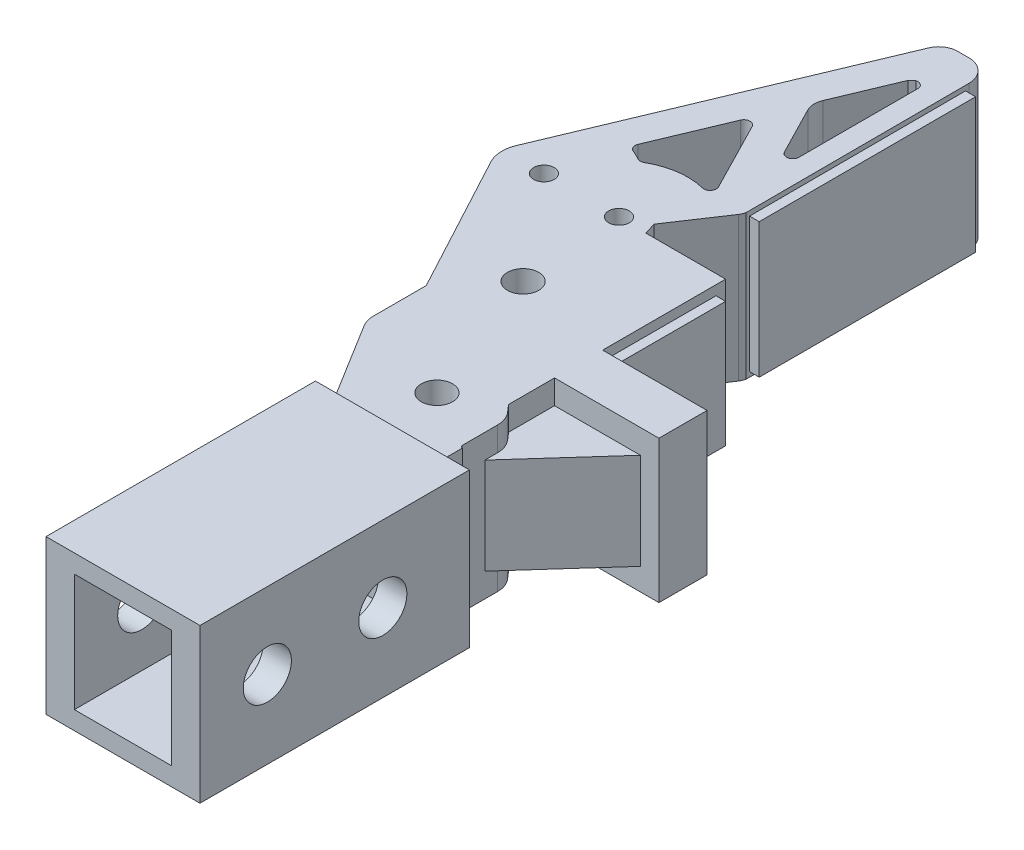
SolidWorks part; units mm, degrees
ref_plane "Alzado" through (0, 0, 0) normal (0, 0, 1) x (1, 0, 0)
ref_plane "Planta" through (0, 0, 0) normal (0, 1, 0) x (1, 0, 0)
ref_plane "Vista lateral" through (0, 0, 0) normal (1, 0, 0) x (0, 0, -1)
sketch "Croquis1" plane through (0, 0, 0) normal (0, 1, 0) x (1, 0, 0)
  line L0 (18.6195, -63.7365) -> (15.4788, -71.2468)
  line L1 (23.4981, -70.8922) -> (19.7973, -63.6902)
  line L2 (21.2126, -59.3337) -> (23.7797, -64.3294)
  line L3 (23.7582, -51.4483) -> (21.148, -57.6901)
  line L4 (25.0079, -64.0323) -> (25.0079, -51.699)
  line L9 (9.2725, -77.6641) -> (10.2186, -75.4015)
  line L10 (10.6346, -74.4068) -> (10.2186, -75.4015)
  line L11 (10.6346, -74.4068) -> (21.907, -47.451)
  line L13 (23.7058, -46.262) -> (24.8929, -46.2648)
  line L14 (27.544, -96.0434) -> (32.8286, -102.1422)
  line L15 (33.4392, -103.7794) -> (33.4392, -107.4469)
  line L16 (22.5204, -109.7992) -> (17.5627, -101.778)
  line L17 (17.1892, -89.4522) -> (17.1892, -100.4636)
  line L18 (23.7582, -51.4483) -> (24.195, -51.0698)
  line L19 (26.9334, -90.9455) -> (26.9334, -94.4063)
  line L20 (17.1892, -94.9579) -> (9.4071, -80.4546)
  line L21 (26.9334, -90.9455) -> (23.879, -78.8216)
  line L24 (22.5204, -109.7992) -> (33.6892, -109.7992)
  line L25 (33.6892, -107.6969) -> (33.6892, -109.7992)
  line L30 (23.879, -78.8216) -> (23.4981, -77.5902)
  line L31 (25.0353, -77.0872) -> (22.7227, -80.5561) construction
  line L32 (24.2033, -76.5325) -> (21.8906, -80.0014) construction
  line L35 (27.1871, -48.5593) -> (27.2389, -71.7765)
  line L36 (26.9975, -72.3412) -> (25.0143, -75.316)
  line L37 (24.2033, -76.5325) -> (25.0143, -75.316)
  line L38 (24.2033, -76.5325) -> (23.4981, -77.5902)
  line L39 (18.0704, -94.4851) -> (10.2882, -79.9818) construction
  line L40 (10.1951, -78.0499) -> (11.1412, -75.7873) construction
  line L41 (11.5572, -74.7926) -> (11.1412, -75.7873) construction
  line L42 (11.5572, -74.7926) -> (22.8287, -47.8391) construction
  line L43 (23.7035, -47.262) -> (25.2842, -47.2658) construction
  line L44 (25.0353, -77.0872) -> (25.8463, -75.8707) construction
  line L45 (27.8414, -72.8781) -> (25.8463, -75.8707) construction
  line L46 (28.1876, -48.7788) -> (28.2392, -71.8971) construction
  arc A0 (23.2652, -71.7401) -> (23.4981, -70.8922) centre (22.92, -71.1893) ccw
  arc A1 (22.7613, -71.8197) -> (22.8172, -71.8312) centre (22.92, -71.1893) ccw
  arc A2 (22.8172, -71.8312) -> (23.2652, -71.7401) centre (22.92, -71.1893) ccw
  arc A3 (22.7613, -71.8197) -> (17.441, -72.5613) centre (21.016, -78.7534) ccw
  arc A4 (17.116, -72.6484) -> (17.441, -72.5613) centre (17.116, -71.9984) ccw
  arc A5 (16.791, -72.5613) -> (17.116, -72.6484) centre (17.116, -71.9984) ccw
  arc A6 (16.791, -72.5613) -> (15.8399, -72.1022) centre (13.216, -78.7534) ccw
  arc A7 (15.4943, -71.7826) -> (15.8399, -72.1022) centre (16.0785, -71.4976) ccw
  arc A8 (15.4788, -71.2468) -> (15.4943, -71.7826) centre (16.0785, -71.4976) ccw
  arc A9 (19.7973, -63.6902) -> (19.0563, -63.358) centre (19.2191, -63.9873) ccw
  arc A10 (19.0563, -63.358) -> (18.6195, -63.7365) centre (19.2191, -63.9873) ccw
  arc A11 (24.7509, -64.5501) -> (25.0079, -64.0323) centre (24.3579, -64.0323) ccw
  arc A12 (23.7797, -64.3294) -> (24.7509, -64.5501) centre (24.3579, -64.0323) ccw
  arc A13 (21.0967, -59.058) -> (21.2126, -59.3337) centre (22.947, -58.4424) ccw
  arc A14 (21.148, -57.6901) -> (21.0967, -59.058) centre (22.947, -58.4424) ccw
  arc A15 (25.0079, -51.699) -> (24.7509, -51.1813) centre (24.3579, -51.699) ccw
  arc A16 (24.7509, -51.1813) -> (24.195, -51.0698) centre (24.3579, -51.699) ccw
  arc A20 (9.2725, -77.6641) -> (9.4071, -80.4546) centre (12.2709, -78.918) ccw
  arc A21 (23.7058, -46.262) -> (21.907, -47.451) centre (23.7012, -48.2102) ccw
  circle A23 centre (21.016, -78.7534) radius 1.0725
  circle A24 centre (13.216, -78.7534) radius 1.0725
  arc A25 (26.9334, -94.4063) -> (27.544, -96.0434) centre (29.4334, -94.4063) ccw
  arc A26 (33.4392, -103.7794) -> (32.8286, -102.1422) centre (30.9392, -103.7794) ccw
  arc A27 (33.4392, -107.4469) -> (33.6892, -107.6969) centre (33.6892, -107.4469) ccw
  arc A28 (17.1892, -100.4636) -> (17.5627, -101.778) centre (19.6892, -100.4636) ccw
  circle A33 centre (27.3927, -104.0488) radius 1.625
  circle A34 centre (21.8402, -89.5423) radius 1.625
  arc A48 (24.8929, -46.2648) -> (27.1871, -48.5593) centre (24.8875, -48.5644) cw
  arc A51 (26.9975, -72.3412) -> (27.2389, -71.7765) centre (25.0687, -71.1826) ccw
  arc A54 (10.1951, -78.0499) -> (10.2882, -79.9818) centre (12.2709, -78.918) ccw construction
  arc A55 (23.7035, -47.262) -> (22.8287, -47.8391) centre (23.7012, -48.2102) ccw construction
  arc A56 (27.1871, -48.5593) -> (25.2842, -47.2658) centre (26.1828, -47.9903) ccw construction
  arc A58 (27.8414, -72.8781) -> (28.2392, -71.8971) centre (25.0687, -71.1826) ccw construction
  arc A76 (28.1876, -48.7788) -> (24.8929, -46.2648) centre (26.1828, -47.9903) ccw construction
  dimension "D2" = 0.25
  dimension "D1" = 1
extrude "Saliente-Extruir1" add sketch "Croquis1" along normal mid plane 15
sketch "Sketch2" plane through (0, 7.5, 0) normal (0, 1, 0) x (1, 0, 0)
sketch "Sketch4" plane through (0, 7.5, 0) normal (0, 1, 0) x (1, 0, 0)
  line L0 (23.879, -78.8216) -> (32.1644, -78.8216)
  line L1 (32.1644, -78.8216) -> (32.1644, -101.3757)
  line L2 (27.544, -96.0434) -> (32.8286, -102.1422) construction
  line L3 (17.7401, -35.423) -> (25.2834, -40.7304)
  line L4 (25.2834, -40.7304) -> (17.7401, -59.6041)
  line L5 (17.7401, -59.6041) -> (17.7401, -35.423)
  line L7 (26.9334, -90.9455) -> (26.9334, -94.4063) construction
  line L9 (27.544, -96.0434) -> (32.1644, -101.3757)
  line L10 (26.9334, -90.9455) -> (26.9334, -94.4063)
  line L15 (26.9334, -90.9455) -> (23.879, -78.8216) construction
  line L16 (26.9334, -90.9455) -> (23.879, -78.8216)
  line L17 (32.9334, -90.2014) -> (29.6972, -77.3559) construction
  line L19 (32.9334, -93.1008) -> (36.699, -97.4466) construction
  line L20 (32.9334, -90.2014) -> (32.9334, -93.1008) construction
  arc A1 (26.9334, -94.4063) -> (27.544, -96.0434) centre (29.4334, -94.4063) ccw construction
  arc A3 (26.9334, -94.4063) -> (27.544, -96.0434) centre (29.4334, -94.4063) ccw
  arc A5 (26.3567, -56.7968) -> (26.4685, -56.8198) centre (26.6741, -55.5361) ccw
  arc A6 (32.9334, -93.1008) -> (32.9334, -93.1008) centre (32.9334, -93.1008) ccw
  dimension "D1" = 6
extrude "Boss-Extrude1" add sketch "Sketch4" against normal through all
sketch "Sketch7" plane through (0, 0, 109.7992) normal (0, 0, 1) x (1, 0, 0)
  line L0 (22.5204, 7.5) -> (22.5204, -7.5) construction
  line L1 (20.5204, 8) -> (20.5204, -8)
  line L2 (20.5204, -8) -> (36.5204, -8)
  line L4 (36.5204, 8) -> (36.5204, -8)
  line L5 (28.1048, 7.5) -> (28.1048, -26.4269) construction
  line L6 (22.5204, 7.5) -> (33.6892, 7.5) construction
  line L12 (20.5204, 8) -> (36.5204, 8)
  point P6 (28.1048, 0)
  dimension "D2" = 8
  dimension "D3" = 16
  dimension "D1" = 16
  dimension "D4" = 2
extrude "Boss-Extrude2" add sketch "Sketch7" along normal blind 28 contours L4 L2 L1 L12
sketch "Sketch8" plane through (20.5204, 0, 0) normal (-1, 0, 0) x (0, 0, 1)
  circle A2 centre (130.7992, 0.1) radius 2.5 construction
  circle A3 centre (118.7992, 0.1) radius 2.5 construction
  circle A4 centre (130.7992, 0.1) radius 2.5
  circle A5 centre (118.7992, 0.1) radius 2.5
sketch "Sketch9" plane through (0, 0, 137.7992) normal (0, 0, 1) x (1, 0, 0)
  line L0 (33.5704, 0) -> (30.5993, 0) construction
  line L2 (23.4704, -6.1) -> (33.5704, -6.1)
  line L9 (23.4704, -6.1) -> (23.4704, 6.1)
  line L10 (23.4704, 6.1) -> (33.5704, 6.1)
  line L14 (33.5704, -6.1) -> (33.5704, 6.1)
  line L15 (23.4704, -6.1) -> (33.5704, 6.1) construction
  line L16 (23.4704, 6.1) -> (33.5704, -6.1) construction
  line L17 (36.5204, 0) -> (35.0984, 0) construction
  line L18 (36.5204, 8) -> (36.5204, -8) construction
  line L19 (28.5204, -8) -> (28.5204, -6.7157) construction
  line L20 (20.5204, -8) -> (36.5204, -8) construction
  line L21 (28.5204, -6.1) -> (28.5204, -2.9602) construction
  point P0 (28.5204, 0)
  dimension "D1" = 10.1
  dimension "D2" = 12.2
ref_plane "Plane1" through (26.5204, 0, 0) normal (-1, 0, 0) x (0, 0, 1)
sketch "Sketch10" plane through (26.5204, 0, 0) normal (-1, 0, 0) x (0, 0, 1)
  line L0 (113.9471, 8) -> (109.7992, 7.5)
  line L1 (137.7992, 8) -> (109.7992, 8) construction
  line L2 (109.7992, 7.5) -> (109.7992, 8)
  line L3 (109.7992, 8) -> (113.9471, 8)
  line L4 (137.7992, 0) -> (128.384, 0) construction
  line L5 (137.7992, 8) -> (137.7992, -8) construction
  line L6 (113.9471, -8) -> (109.7992, -7.5)
  line L7 (109.7992, -8) -> (113.9471, -8)
  line L8 (109.7992, -7.5) -> (109.7992, -8)
extrude "Boss-Extrude3" add sketch "Sketch10" along normal mid plane 8 contours L3 L0 L2 | L6 L8 L7
extrude "Cut-Extrude6" cut sketch "Sketch8" against normal blind 30
ref_plane "Plane2" through (0, -7, 0) normal (0, -1, 0) x (-1, 0, 0)
sketch "Sketch11" plane through (0, -7, 0) normal (0, -1, 0) x (-1, 0, 0)
  line L0 (-27.1871, -48.5593) -> (-27.2389, -71.7765) construction
  line L1 (-27.1879, -48.9189) -> (-27.2381, -71.4007)
  line L3 (-27.1879, -48.9189) -> (-28.2381, -48.9189)
  line L5 (-27.2381, -71.4007) -> (-28.2381, -71.4007)
  line L6 (-28.2381, -48.9189) -> (-28.2381, -71.4007)
  dimension "D1" = 1
extrude "Boss-Extrude4" add sketch "Sketch11" against normal blind 14
sketch "Sketch12" plane through (32.1644, 0, 0) normal (1, 0, 0) x (0, 0, -1)
  line L0 (-94.9579, -7.3) -> (-100.4636, -7.3) construction
  line L5 (-78.8216, 7.5) -> (-101.3757, 7.5) construction
  line L6 (-101.6002, -7.5) -> (-101.6002, 7.5) construction
  line L17 (-96.6002, -7.3) -> (-91.6002, -7.3)
  line L18 (-91.6002, -7.3) -> (-91.6002, 7.5)
  line L19 (-91.6002, 7.5) -> (-96.6002, 7.5)
  line L20 (-96.6002, 7.5) -> (-96.6002, -7.3)
  dimension "D1" = 5
  dimension "D2" = 5
extrude "Boss-Extrude5" add sketch "Sketch12" along normal blind 10.85
sketch "Sketch13" plane through (32.1644, 0, 0) normal (1, 0, 0) x (0, 0, -1)
  line L1 (-90.6002, 6.5) -> (-79.8216, 6.5)
  line L2 (-90.6002, 6.5) -> (-90.6002, -6.5)
  line L3 (-90.6002, -6.5) -> (-79.8216, -6.5)
  line L4 (-79.8216, 6.5) -> (-79.8216, -6.5)
  line L7 (-91.6002, -7.3) -> (-91.6002, 7.5) construction
  line L8 (-78.8216, -7.5) -> (-78.8216, 7.5) construction
  line L9 (-78.8216, -7.5) -> (-101.3757, -7.5) construction
  line L10 (-78.8216, 7.5) -> (-91.6002, 7.5) construction
  dimension "D1" = 1
  dimension "D2" = 1
  dimension "D3" = 1
  dimension "D4" = 1
extrude "Boss-Extrude6" add sketch "Sketch13" along normal blind 1
sketch "Sketch14" plane through (0, 0, 0) normal (0, 1, 0) x (1, 0, 0)
  line L0 (20.5204, -109.7992) -> (20.2925, -106.1946)
  line L1 (22.5204, -109.7992) -> (17.5627, -101.778) construction
  line L2 (20.2925, -106.1946) -> (22.5204, -109.7992)
  line L3 (22.5204, -109.7992) -> (20.5204, -109.7992)
extrude "Boss-Extrude7" add sketch "Sketch14" along normal mid plane 10
extrude "Cut-Extrude7" cut sketch "Sketch9" against normal blind 25.5
sketch "Sketch15" plane through (0, 0, 0) normal (0, 1, 0) x (1, 0, 0)
  line L0 (33.4392, -105.1121) -> (41.0828, -96.6002)
  line L1 (33.4392, -103.7794) -> (33.4392, -107.4469) construction
  line L2 (43.0144, -96.6002) -> (32.1644, -96.6002) construction
  line L3 (41.0828, -96.6002) -> (32.1644, -96.6002)
  line L4 (32.1644, -101.3757) -> (32.8286, -102.1422) construction
  line L5 (32.1644, -96.6002) -> (32.1644, -101.3757) construction
  line L6 (33.4392, -103.7794) -> (33.4392, -105.1121)
  line L7 (32.1644, -101.3757) -> (32.8286, -102.1422)
  line L8 (32.1644, -96.6002) -> (32.1644, -101.3757)
  arc A0 (33.4392, -103.7794) -> (32.8286, -102.1422) centre (30.9392, -103.7794) ccw construction
  arc A1 (33.4392, -103.7794) -> (32.8286, -102.1422) centre (30.9392, -103.7794) ccw
  point P11 (33.4392, -105.3209)
extrude "Boss-Extrude8" add sketch "Sketch15" along normal mid plane 10
